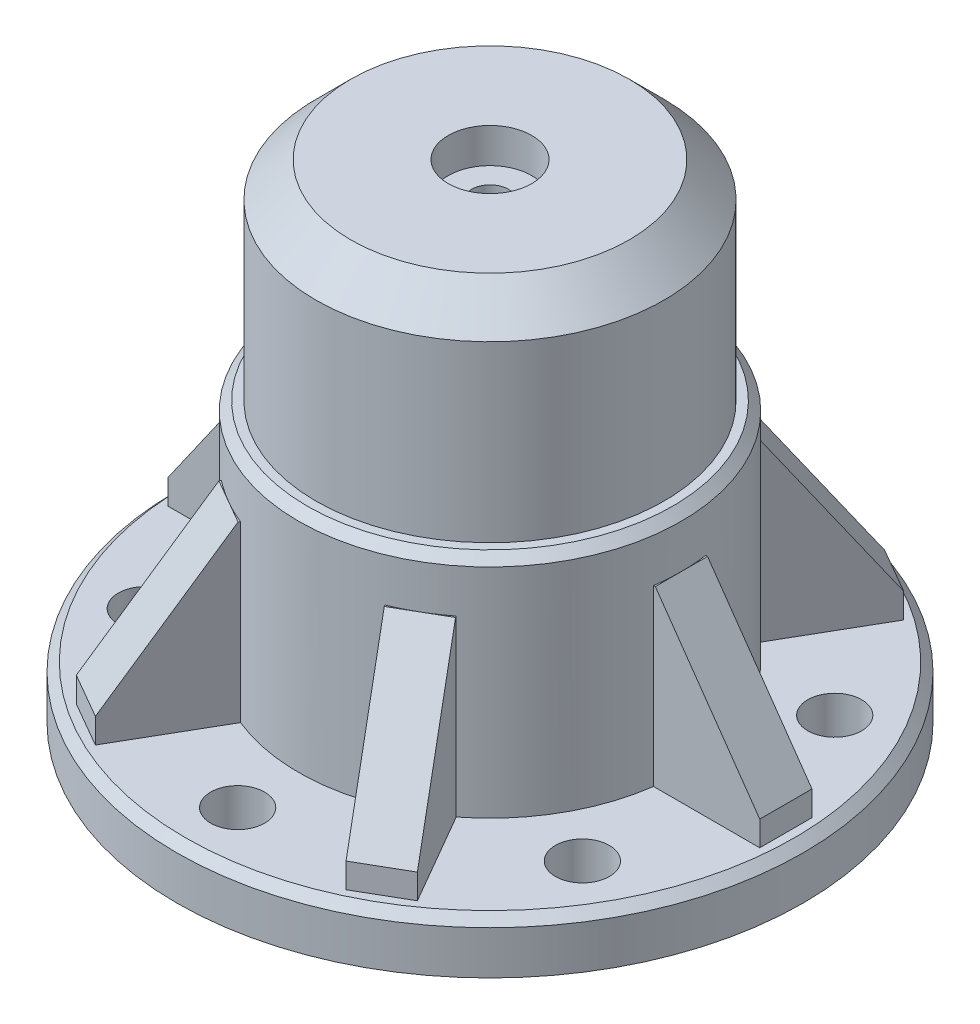
SolidWorks part; units mm, degrees
ref_plane "Front Plane" through (0, 0, 0) normal (0, 0, 1) x (1, 0, 0)
ref_plane "Top Plane" through (0, 0, 0) normal (0, 1, 0) x (1, 0, 0)
ref_plane "Right Plane" through (0, 0, 0) normal (1, 0, 0) x (0, 0, -1)
sketch "Sketch1" plane through (0, 0, 0) normal (0, 1, 0) x (1, 0, 0)
  circle A0 centre (0, 0) radius 8
  circle A1 centre (0, 0) radius 18
  dimension "D1" = 16
  dimension "D2" = 10
extrude "Boss-Extrude1" add sketch "Sketch1" along normal blind 3
sketch "Sketch2" plane through (0, 3, 0) normal (0, 1, 0) x (1, 0, 0)
  circle A0 centre (0, 0) radius 11
  circle A1 centre (0, 0) radius 8 construction
  circle A2 centre (0, 0) radius 8
  dimension "D1" = 3
extrude "Boss-Extrude2" add sketch "Sketch2" along normal blind 22
sketch "Sketch3" plane through (0, 3, 0) normal (0, 1, 0) x (1, 0, 0)
  line L0 (0, 0) -> (18, 0) construction
  line L1 (0, 0) -> (15.5885, -9) construction
  line L2 (9.5263, -5.5) -> (15.5885, -9) construction
  circle A0 centre (0, 0) radius 18 construction
  circle A1 centre (0, 0) radius 11 construction
  circle A2 centre (0, 0) radius 11
  point P10 (12.5574, -7.25)
  point P14 (0, -14.5)
  point P15 (-12.5574, -7.25)
  point P16 (-12.5574, 7.25)
  point P17 (0, 14.5)
  point P18 (12.5574, 7.25)
  point P19 (0, 0)
  dimension "D1" = 30
  dimension "D2" = 6
ref_point "Point1"
ref_point "Point2"
ref_point "Point3"
hole_wizard "M (0.295) Diameter Hole1" positions "3DSketch1" profile "Sketch4" hole size "M" standard "ANSI Inch" end condition through all
sketch3d "3DSketch1"
  point P0 (0, 3, 14.5)
  point P3 (-12.5574, 3, 7.25)
  point P6 (12.5574, 3, 7.25)
  point P9 (12.5574, 3, -7.25)
  point P12 (0, 3, -14.5)
  point P15 (-12.5574, 3, -7.25)
sketch "Sketch4" plane through (0, 3, 14.5) normal (1, 0, 0) x (0, 0, 1)
  line L0 (0, 0) -> (0, 3)
  line L1 (0, 3) -> (1.55, 3)
  line L2 (1.55, 3) -> (1.55, 0)
  line L5 (1.55, 0) -> (0, 0)
  line L11 (0, -6.35) -> (0, 107.95) construction
  dimension "Thru Hole Dia." = 3.1
  dimension "Thru Hole Depth" = 3
ref_plane "Plane1" through (0, 0, 0) normal (0, 0, 1) x (1, 0, 0)
sketch "Sketch5" plane through (0, 0, 0) normal (0, 0, 1) x (1, 0, 0)
  line L0 (18, 3) -> (11, 13) construction
  line L1 (11, 3) -> (11, 25) construction
  line L2 (11, 3) -> (-11, 3) construction
  line L3 (11, 13) -> (17, 4.4286)
  line L5 (17, 4.4286) -> (17, 3)
  line L6 (17, 3) -> (17, 2.5)
  line L7 (11, 13) -> (10.5, 13)
  line L9 (10.5, 13) -> (10.5, 2.5)
  line L10 (10.5, 2.5) -> (17, 2.5)
  dimension "D1" = 10
  dimension "D2" = 1
  dimension "D3" = 0.5
  dimension "D4" = 0.5
extrude "Boss-Extrude3" add sketch "Sketch5" along normal mid plane 3
ref_axis "Axis1" through (0, 18, 0) along (0, -1, 0)
pattern_circular "CirPattern1" count 6 over 360 about axis through (0, 18, 0) along (0, -1, 0) of "Boss-Extrude3"
chamfer "Chamfer2" distance 0.5 angle 45 1 edges at (0, 3, 18)
sketch "Sketch6" plane through (0, 25, 0) normal (0, 1, 0) x (1, 0, 0)
  circle A0 centre (0, 0) radius 11
extrude "Boss-Extrude4" add sketch "Sketch6" along normal blind 3
sketch "Sketch8" plane through (0, 25, 0) normal (0, -1, 0) x (1, 0, 0)
  circle A1 centre (0, 0) radius 8
  circle A2 centre (0, 0) radius 8
  dimension "D1" = 0
extrude "Boss-Extrude5" add sketch "Sketch8" along normal blind 2
chamfer "Chamfer3" distance 3 angle 45 2 edges at (0, 28, 11) (0, 23, -8)
sketch "Sketch7" plane through (0, 28, 0) normal (0, 1, 0) x (1, 0, 0)
  circle A0 centre (0, 0) radius 2.4
  dimension "D1" = 4.8
extrude "Cut-Extrude1" cut sketch "Sketch7" against normal blind 2
sketch "Sketch9" plane through (0, 26, 0) normal (0, 1, 0) x (1, 0, 0)
  circle A0 centre (0, 0) radius 1.05
  dimension "D1" = 2.1
extrude "Cut-Extrude2" cut sketch "Sketch9" against normal up to next
sketch "Sketch10" plane through (0, 28, 0) normal (0, 1, 0) x (1, 0, 0)
  circle A0 centre (0, 0) radius 10
  circle A1 centre (0, 0) radius 11 construction
  circle A2 centre (0, 0) radius 11
  dimension "D1" = 1
extrude "Cut-Extrude3" cut sketch "Sketch10" against normal blind 12
chamfer "Chamfer4" distance 0.5 angle 45 1 edges at (0, 16, 11)
